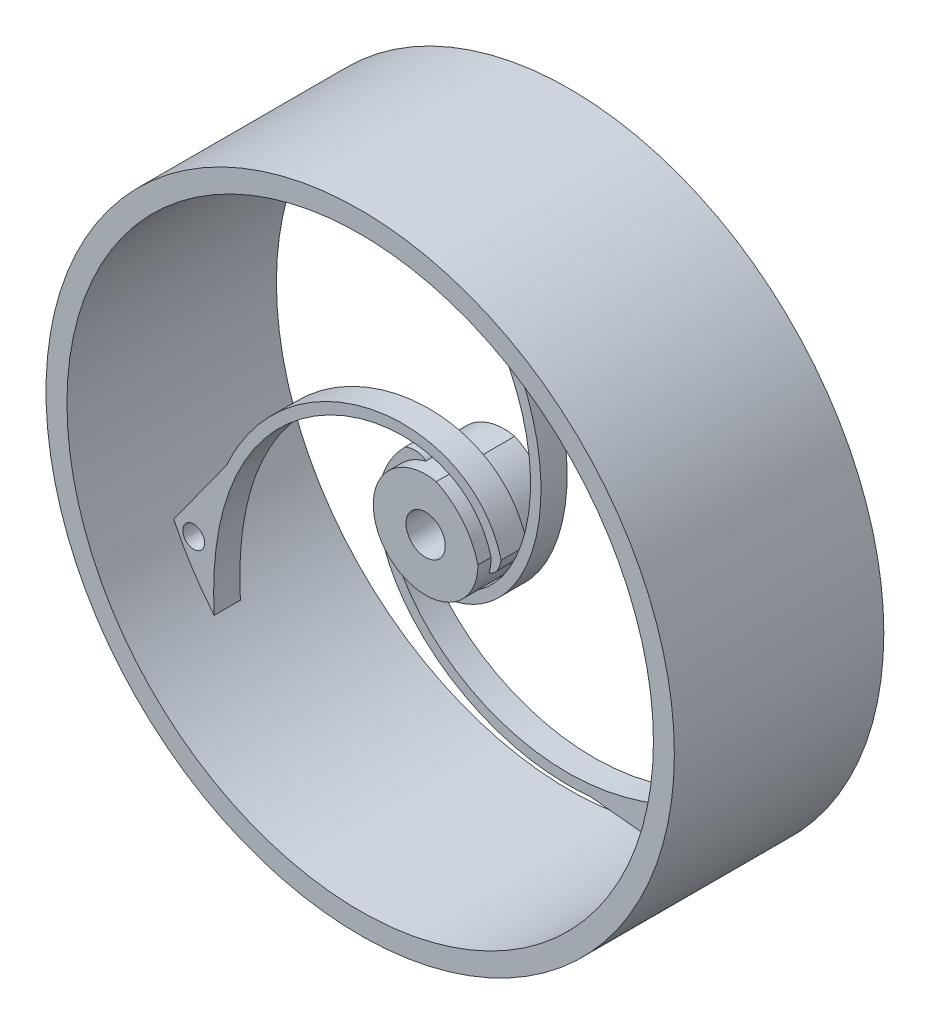
SolidWorks part; units mm, degrees
ref_plane "Front Plane" through (0, 0, 0) normal (0, 0, 1) x (1, 0, 0)
ref_plane "Top Plane" through (0, 0, 0) normal (0, 1, 0) x (1, 0, 0)
ref_plane "Right Plane" through (0, 0, 0) normal (1, 0, 0) x (0, 0, -1)
sketch "Sketch1" plane through (0, 0, 0) normal (0, 0, 1) x (1, 0, 0)
  line L0 (12.7, 0) -> (5.4399, 27.7018) construction
  line L1 (5.4399, 27.7018) -> (-42.4793, 17.8404) construction
  line L2 (-42.4793, 17.8404) -> (-56.2272, -12.7705) construction
  line L3 (-56.2272, -12.7705) -> (-54.4581, -45.7425) construction
  circle A0 centre (0, 0) radius 76.2
  circle A1 centre (0, 0) radius 71.12
  circle A2 centre (0, 0) radius 12.7
  circle A3 centre (0, 0) radius 4.7625
  circle A4 centre (-59.435, -31.7131) radius 2.6521
  spline S0 degree 4 poles (12.7, 0) (5.4399, 27.7018) (-42.4793, 17.8404) (-56.2272, -12.7705) (-54.4581, -45.7425) knots 0 0 0 0 0 1 1 1 1 1
  spline S1 degree 1 poles (15.157, 0.6439) (-56.9944, -45.8785) knots 0 0 1 1 construction
  spline S2 degree 3 poles (15.157, 0.6439) (14.9914, 1.2758) (14.6049, 2.541) (13.668, 4.8874) (12.1832, 7.5567) (9.9697, 10.295) (6.5346, 13.3269) (1.5201, 15.964) (-5.1689, 17.4469) (-12.1891, 17.437) (-21.6354, 15.6344) (-33.0135, 10.3435) (-43.697, 0.6838) (-49.4886, -8.3131) (-52.736, -15.5018) (-54.8005, -21.5262) (-56.4296, -29.1897) (-57.071, -36.0642) (-57.1595, -41.6499) (-57.0699, -44.4728) (-56.9944, -45.8785) knots 0 0 0 0 0.015625 0.03125 0.0625 0.09375 0.125 0.1875 0.25 0.3125 0.375 0.5 0.625 0.725481 0.756731 0.8125 0.875 0.9375 0.96875 1 1 1 1
  spline S3 degree 2 poles (15.157, 0.6439) (14.1652, -4.3046) (10.2781, -3.3624) knots 0 0 0 1 1 1
  spline S4 degree 1 poles (-51.4897, -12.7703) (-64.2647, -30.4649) knots 0 0 1 1
  dimension "D1" = 152.4
  dimension "D3" = 25.4
  dimension "D4" = 9.525
  dimension "D2" = 5.08
  dimension "D5" = 2.54
extrude "Boss-Extrude8" add sketch "Sketch1" along normal mid plane 50.8 contours A0 A1 region at (-74.0447, 0, 0)
extrude "Boss-Extrude9" add sketch "Sketch1<3>" along normal blind 6.35 contours S2 S4 A1 A4 | S3 S2 A1 S0 A2 | S0 A2 region at (-58.3277, -28.5256, 0) region at (-55.06, -43.4841, 0) region at (9.0901, 7.3705, 0)
sketch "Sketch1<3>" plane through (0, 0, 0) normal (0, 0, 1) x (1, 0, 0) same geometry as "Sketch1"
extrude "Boss-Extrude10" add sketch "Sketch1<4>" along normal mid plane 19.05 contours A2 S0 A3 region at (8.7604, 7.1391, 0)
sketch "Sketch1<4>" plane through (0, 0, 0) normal (0, 0, 1) x (1, 0, 0) same geometry as "Sketch1"
ref_axis "Axis2" through (0, 0, -27.94) along (0, 0, 1)
pattern_circular "CirPattern2" count 3 over 360 about axis through (0, 0, -27.94) along (0, 0, 1) of "Boss-Extrude9"
